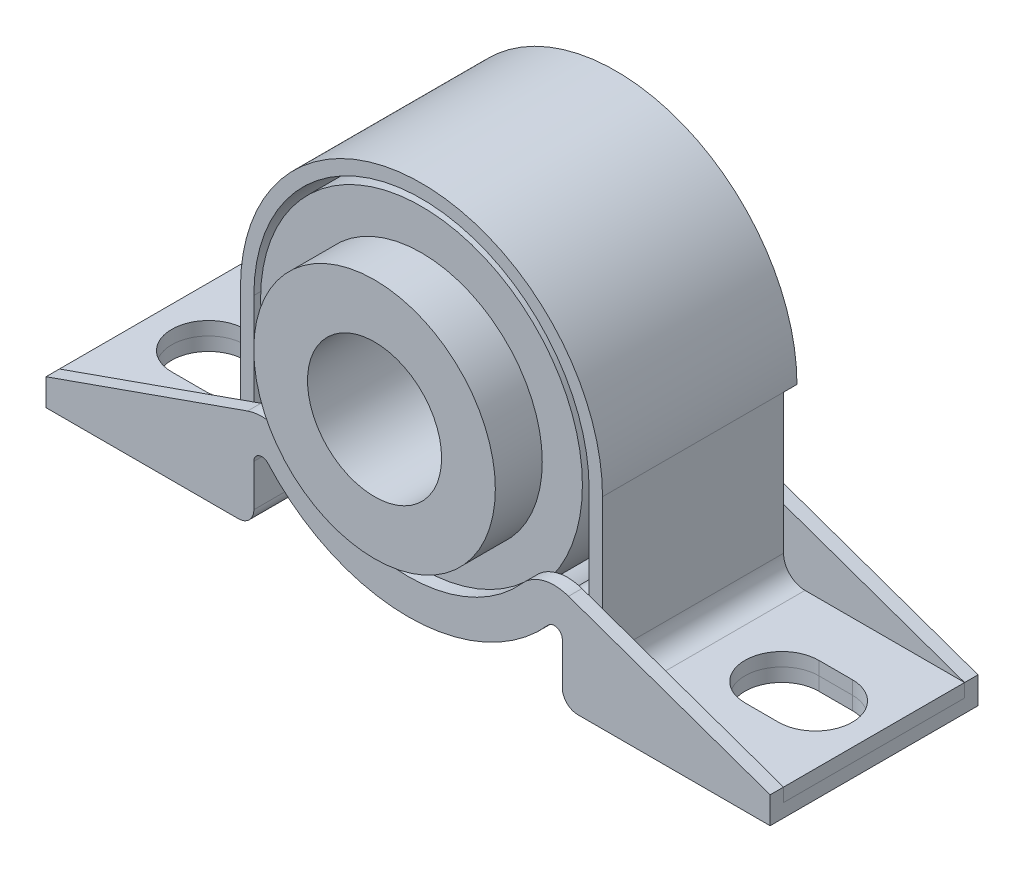
SolidWorks part; units mm, degrees
material "Alloy Steel"
ref_plane "Front" through (0, 0, 0) normal (0, 0, 1) x (1, 0, 0)
ref_plane "Top" through (0, 0, 0) normal (0, 1, 0) x (1, 0, 0)
ref_plane "Right" through (0, 0, 0) normal (1, 0, 0) x (0, 0, -1)
sketch "Sketch1" plane through (0, 0, 0) normal (0, 0, 1) x (1, 0, 0)
  line L1 (-23.9712, -19.05) -> (-42.8625, -19.05) construction
  line L2 (-42.8625, -19.05) -> (-42.8625, -22.225) construction
  line L3 (-42.8625, -22.225) -> (42.8625, -22.225) construction
  line L6 (0, 0) -> (0, -22.225) construction
  line L9 (42.8625, -22.225) -> (42.8625, -19.05) construction
  line L10 (42.8625, -19.05) -> (23.9713, -19.05) construction
  line L12 (-21.4313, 0) -> (-21.4312, -16.51) construction
  line L13 (-42.8625, -20.6375) -> (-19.8438, -20.6375)
  line L14 (21.4313, 0) -> (21.4313, -16.51) construction
  line L15 (-19.8438, -20.6375) -> (-19.8438, -15.42)
  line L16 (19.8438, -15.42) -> (19.8438, -20.6375)
  line L17 (19.8438, -20.6375) -> (42.8625, -20.6375)
  circle A0 centre (0, 0) radius 6.35 construction
  circle A1 centre (0, 0) radius 14.3002 construction
  arc A2 (21.4313, 0) -> (-21.4313, 0) centre (0, 0) ccw construction
  arc A5 (-21.4312, -16.51) -> (-23.9712, -19.05) centre (-23.9712, -16.51) cw construction
  arc A6 (21.4313, -16.51) -> (23.9713, -19.05) centre (23.9713, -16.51) ccw construction
  arc A7 (-19.8438, -15.42) -> (-15.4074, -13.7301) centre (-17.3038, -15.42) cw
  arc A8 (-15.4074, -13.7301) -> (15.4074, -13.7301) centre (0, 0) ccw
  arc A9 (15.4074, -13.7301) -> (19.8438, -15.42) centre (17.3038, -15.42) cw
  dimension "Shaft Dia" = 12.7
  dimension "K" = 28.6004
  dimension "D1" = 2.54
  dimension "w" = 43.6562
  dimension "h" = 22.225
  dimension "g" = 3.175
  dimension "a" = 85.725
  dimension "D2" = 1.5875
extrude "Extrude-Thin2" add sketch "Sketch1" along normal mid plane 24.6062 thin thin type one direction wall 1.5875
sketch "Sketch4" plane through (0, 0, 12.3031) normal (0, 0, 1) x (1, 0, 0)
  line L0 (-42.8625, -19.05) -> (-18.9938, -10.6294)
  line L1 (18.9938, -10.6294) -> (42.8625, -19.05)
  line L2 (-23.9712, -19.05) -> (-42.8625, -19.05) construction
  line L3 (42.8625, -19.05) -> (23.9713, -19.05) construction
  line L10 (20.0978, -22.225) -> (42.8625, -22.225)
  line L11 (42.8625, -22.225) -> (42.8625, -20.6375)
  line L12 (42.8625, -20.6375) -> (20.0978, -20.6375)
  line L13 (19.8438, -20.3835) -> (19.8438, -15.42)
  line L14 (-19.8438, -15.42) -> (-19.8438, -20.3835)
  line L15 (-20.0978, -20.6375) -> (-42.8625, -20.6375)
  line L16 (-42.8625, -20.6375) -> (-42.8625, -22.225)
  line L17 (-42.8625, -22.225) -> (-20.0978, -22.225)
  line L18 (-18.2563, -20.3835) -> (-18.2563, -15.42)
  line L19 (18.2563, -15.42) -> (18.2563, -20.3835)
  line L20 (20.0978, -22.225) -> (42.8625, -22.225)
  line L21 (42.8625, -22.225) -> (42.8625, -19.05)
  line L26 (-42.8625, -19.05) -> (-42.8625, -22.225)
  line L27 (-42.8625, -22.225) -> (-20.0978, -22.225)
  line L28 (-18.2563, -20.3835) -> (-18.2563, -15.42)
  line L29 (18.2563, -15.42) -> (18.2563, -20.3835)
  arc A0 (-13.5111, -12.0403) -> (-18.9938, -10.6294) centre (-17.3038, -15.42) ccw
  arc A1 (18.9938, -10.6294) -> (13.5111, -12.0403) centre (17.3038, -15.42) ccw
  arc A2 (-13.5111, -12.0403) -> (13.5111, -12.0403) centre (0, 0) ccw
  arc A10 (19.8438, -20.3835) -> (20.0978, -20.6375) centre (20.0978, -20.3835) ccw
  arc A11 (19.8438, -15.42) -> (15.4074, -13.7301) centre (17.3038, -15.42) ccw
  arc A12 (-15.4074, -13.7301) -> (15.4074, -13.7301) centre (0, 0) ccw
  arc A13 (-15.4074, -13.7301) -> (-19.8438, -15.42) centre (-17.3038, -15.42) ccw
  arc A14 (-20.0978, -20.6375) -> (-19.8438, -20.3835) centre (-20.0978, -20.3835) ccw
  arc A15 (-20.0978, -22.225) -> (-18.2563, -20.3835) centre (-20.0978, -20.3835) ccw
  arc A17 (-16.5926, -14.7863) -> (16.5926, -14.7863) centre (0, 0) ccw
  arc A19 (18.2563, -20.3835) -> (20.0978, -22.225) centre (20.0978, -20.3835) ccw
  arc A21 (-16.5926, -14.7863) -> (-18.2563, -15.42) centre (-17.3038, -15.42) ccw
  arc A22 (-16.5926, -14.7863) -> (-18.2563, -15.42) centre (-17.3038, -15.42) ccw
  arc A23 (18.2563, -15.42) -> (16.5926, -14.7863) centre (17.3038, -15.42) ccw
  arc A24 (18.2563, -15.42) -> (16.5926, -14.7863) centre (17.3038, -15.42) ccw
  arc A25 (-20.0978, -22.225) -> (-18.2563, -20.3835) centre (-20.0978, -20.3835) ccw
  arc A27 (-16.5926, -14.7863) -> (16.5926, -14.7863) centre (0, 0) ccw
  arc A29 (18.2563, -20.3835) -> (20.0978, -22.225) centre (20.0978, -20.3835) ccw
  dimension "D2" = 5.08
  dimension "D1" = 0
extrude "Extrude1" add sketch "Sketch4" against normal blind 1.5875
mirror "Mirror1" about plane through (0, 0, 0) normal (0, 0, 1) of "Extrude1"
sketch "Sketch5" plane through (0, 0, 0) normal (0, 0, 1) x (1, 0, 0)
  line L0 (42.8625, -19.05) -> (23.9713, -19.05) construction
  line L1 (21.4313, 0) -> (21.4313, -16.51) construction
  line L2 (-21.4313, 0) -> (-21.4312, -16.51) construction
  line L3 (-23.9712, -19.05) -> (-42.8625, -19.05) construction
  line L4 (42.8625, -19.05) -> (23.9713, -19.05)
  line L5 (21.4313, 0) -> (21.4313, -16.51)
  line L6 (-21.4313, 0) -> (-21.4312, -16.51)
  line L7 (-23.9712, -19.05) -> (-42.8625, -19.05)
  arc A0 (21.4313, -16.51) -> (23.9713, -19.05) centre (23.9713, -16.51) ccw construction
  arc A1 (21.4313, 0) -> (-21.4313, 0) centre (0, 0) ccw construction
  arc A2 (-23.9712, -19.05) -> (-21.4312, -16.51) centre (-23.9712, -16.51) ccw construction
  arc A3 (21.4313, -16.51) -> (23.9713, -19.05) centre (23.9713, -16.51) ccw
  arc A4 (21.4313, 0) -> (-21.4313, 0) centre (0, 0) ccw
  arc A5 (-23.9712, -19.05) -> (-21.4312, -16.51) centre (-23.9712, -16.51) ccw
extrude "Extrude-Thin3" add sketch "Sketch5" along normal up to surface (10.7156 mm away) and the other way up to surface (10.7156 mm away) separate body thin up to face at (0, -17.0875, 10.7156) other way up to face at (0, -17.0875, -10.7156) thin type one direction reverse wall 1.5875
sketch "Sketch6" plane through (0, 0, -10.7156) normal (0, 0, -1) x (-1, 0, 0)
  line L0 (-21.4313, 0) -> (21.4313, 0) construction
  line L1 (-19.8438, 0) -> (-21.4313, 0)
  line L2 (21.4313, 0) -> (19.8438, 0)
  arc A0 (21.4313, 0) -> (-21.4313, 0) centre (0, 0) ccw construction
  arc A1 (21.4313, 0) -> (-21.4313, 0) centre (0, 0) ccw
  arc A2 (-13.5111, -12.0403) -> (13.5111, -12.0403) centre (0, 0) ccw construction
  arc A3 (-13.5111, -12.0403) -> (18.0975, 0) centre (0, 0) ccw construction
  arc A4 (18.021, 1.6624) -> (-18.021, 1.6624) centre (0, 0) ccw
  arc A5 (19.8438, 0) -> (-19.8438, 0) centre (0, 0) ccw construction
  arc A6 (19.8438, 0) -> (-19.8438, 0) centre (0, 0) ccw construction
  arc A7 (-19.8438, 0) -> (-18.021, 1.6624) centre (-19.8438, 1.8305) ccw
  arc A8 (19.8438, 0) -> (18.021, 1.6624) centre (19.8438, 1.8305) cw
extrude "Extrude2" add sketch "Sketch6" along normal blind 1.5875
mirror "Mirror2" [suppressed] about plane through (0, 0, 0) normal (0, 0, 1)
sketch "Sketch7" plane through (0, 0, 0) normal (0, 0, 1) x (1, 0, 0)
  circle A0 centre (0, 0) radius 19.05
  circle A1 centre (0, 0) radius 14.3002
  circle A2 centre (0, 0) radius 14.3002 construction
extrude "Extrude3" add sketch "Sketch7" along normal up to surface (10.7156 mm away) and the other way up to surface (10.7156 mm away) separate body up to face at (0, -17.0875, 10.7156) other way up to face at (0, -17.0875, -10.7156)
ref_plane "Plane1" through (0, 0, 16.2719) normal (0, 0, -1) x (-1, 0, 0)
sketch "Sketch8" plane through (0, 0, 16.2719) normal (0, 0, 1) x (1, 0, 0)
  circle A0 centre (0, 0) radius 14.3002 construction
  circle A2 centre (0, 0) radius 14.3002
  circle A3 centre (0, 0) radius 7.9375
extrude "Extrude4" add sketch "Sketch8" against normal blind 21.9989 separate body
sketch "Sketch3" plane through (0, 0, 0) normal (0, 1, 0) x (1, 0, 0)
  line L2 (-35.9172, 0) -> (-31.9484, 0) construction
  line L3 (-31.9484, 0) -> (0, 0) construction
  line L4 (0, 0) -> (31.9484, 0) construction
  line L5 (31.9484, 0) -> (35.9172, 0) construction
  line L6 (-35.9172, 4.3656) -> (-31.9484, 4.3656)
  line L7 (-35.9172, -4.3656) -> (-31.9484, -4.3656)
  line L8 (31.9484, -4.3656) -> (35.9172, -4.3656)
  line L9 (35.9172, 4.3656) -> (31.9484, 4.3656)
  line L10 (-33.9328, -4.3656) -> (-33.9328, 0) construction
  arc A0 (-35.9172, 4.3656) -> (-35.9172, -4.3656) centre (-35.9172, 0) ccw
  arc A1 (-31.9484, 4.3656) -> (-31.9484, -4.3656) centre (-31.9484, 0) cw
  arc A2 (31.9484, 4.3656) -> (31.9484, -4.3656) centre (31.9484, 0) ccw
  arc A3 (35.9172, 4.3656) -> (35.9172, -4.3656) centre (35.9172, 0) cw
  point P13 (33.9328, -4.3656)
  point P14 (-33.9328, -4.3656)
  dimension "D1" = 67.8656
  dimension "D2" = 12.7
  dimension "Slot Width" = 8.7312
extrude "Cut-Extrude1" cut sketch "Sketch3" against normal through all
sketch "Sketch9" plane through (0, 0, 0) normal (1, 0, 0) x (0, 0, -1)
  line L0 (5.7271, 0) -> (-16.2719, 0) construction
  line L3 (-16.2719, 7.9375) -> (-16.2719, -7.9375) construction
  line L4 (5.7271, -7.9375) -> (5.7271, 7.9375) construction
equation "\"D2@Sketch1\"=\"g@Sketch1\"/2"
equation "\"D5@Extrude-Thin2\"=\"g@Sketch1\"/2"
equation "\"D1@Extrude1\"=\"g@Sketch1\"/2"
equation "\"D5@Extrude-Thin3\" = \"g@Sketch1\"/2"
equation "\"D1@Extrude2\"=\"g@Sketch1\"/2"
